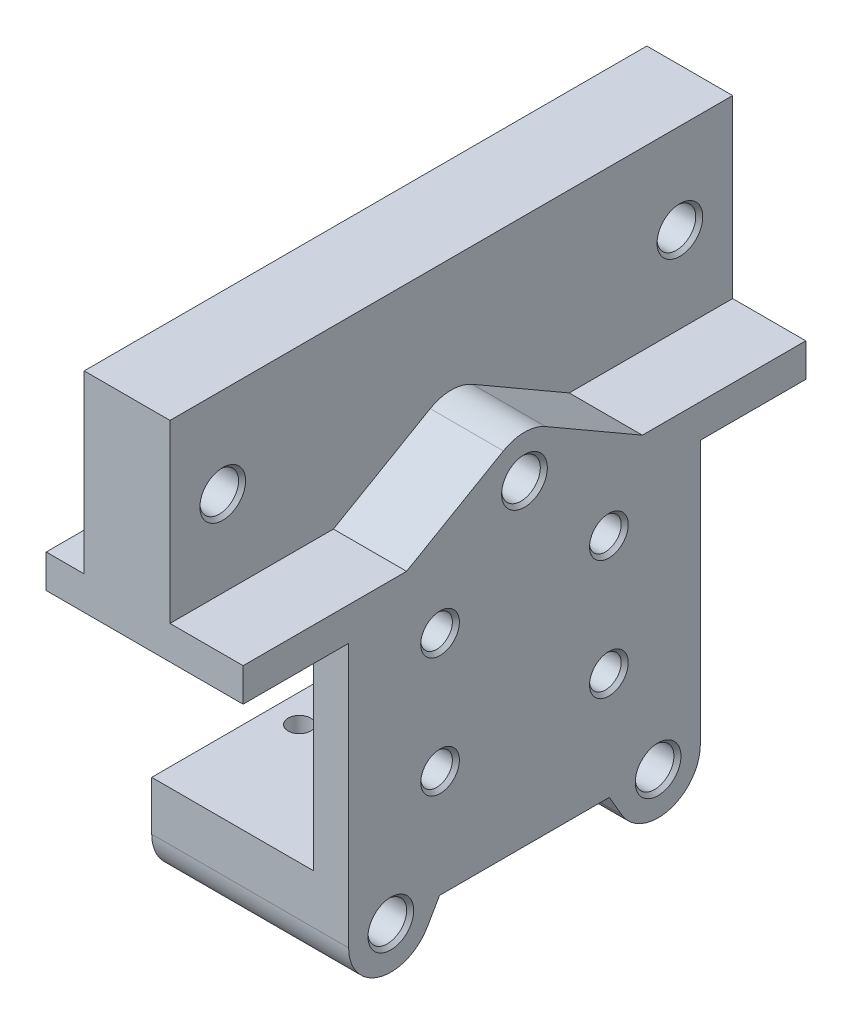
SolidWorks part; units mm, degrees
material "PET"
ref_plane "Front Plane" through (0, 0, 0) normal (0, 0, 1) x (1, 0, 0)
ref_plane "Top Plane" through (0, 0, 0) normal (0, 1, 0) x (1, 0, 0)
ref_plane "Right Plane" through (0, 0, 0) normal (1, 0, 0) x (0, 0, -1)
sketch "Sketch1" plane through (0, 0, 0) normal (0, 0, 1) x (1, 0, 0)
  line L0 (-11.5, 0) -> (16.5, 0)
  line L1 (16.5, 0) -> (16.5, 42.25)
  line L2 (16.5, 42.25) -> (-11.5, 42.25)
  line L3 (11.5, 37.5) -> (11.5, 7)
  line L4 (11.5, 7) -> (-11.5, 7)
  line L8 (-11.5, 7) -> (-11.5, 0)
  line L9 (11.5, 37.5) -> (-11.5, 37.5)
  line L10 (-11.5, 37.5) -> (-11.5, 42.25)
  line L11 (0, 0) -> (0, 42.7189) construction
  point P11 (0, 7)
  dimension "D2" = 23
  dimension "D3" = 5
  dimension "D4" = 7
  dimension "D5" = 30.5
  dimension "D6" = 35.25
extrude "Boss-Extrude1" add sketch "Sketch1" along normal blind 50
sketch "Sketch2" plane through (0, 0, 0) normal (0, -1, 0) x (1, 0, 0)
  line L0 (-11.5, 50) -> (-11.5, 0) construction
  line L3 (-7.5, 17) -> (7.5, 17) construction
  line L4 (-7.5, 17) -> (-7.5, 33) construction
  line L5 (-7.5, 33) -> (7.5, 33) construction
  line L6 (7.5, 17) -> (7.5, 33) construction
  line L7 (-7.5, 17) -> (7.5, 33) construction
  line L8 (-7.5, 33) -> (7.5, 17) construction
  point P5 (0, 25)
  dimension "D1" = 15
  dimension "D2" = 16
  dimension "D3" = 11.5
  dimension "D4" = 25
hole_wizard "Ø3.2 (3.2) Diameter Hole1" positions "Sketch3" profile "Sketch4" hole size "Ø3.2" standard "ANSI Metric" end condition up to next
sketch "Sketch3" plane through (0, 0, 0) normal (0, -1, 0) x (-1, 0, 0)
  point P0 (-7.5, -17)
  point P3 (7.5, -17)
  point P6 (7.5, -33)
  point P9 (-7.5, -33)
sketch "Sketch4" plane through (7.5, 0, 17) normal (1, 0, 0) x (0, 0, -1)
  line L0 (0, 0) -> (0, 7)
  line L1 (0, 7) -> (1.6, 7)
  line L2 (1.6, 7) -> (1.6, 0)
  line L5 (1.6, 0) -> (0, 0)
  line L11 (0, -6.35) -> (0, 107.95) construction
  dimension "Thru Hole Dia." = 3.2
  dimension "Thru Hole Depth" = 7
sketch "Sketch5" plane through (16.5, 0, 0) normal (1, 0, 0) x (0, 0, -1)
  line L0 (-50, 32.25) -> (0, 32.25) construction
  line L1 (-50, 0) -> (-50, 42.25) construction
  line L2 (0, 0) -> (0, 42.25) construction
  line L3 (-50, 42.25) -> (0, 42.25) construction
  line L4 (-50, 15.25) -> (0, 15.25) construction
  line L5 (-13, 32.25) -> (-13, 15.25) construction
  line L6 (-37, 32.25) -> (-37, 15.25) construction
  circle A0 centre (-37, 32.25) radius 2.25
  circle A1 centre (-13, 32.25) radius 2.25
  circle A2 centre (-37, 15.25) radius 2.25
  circle A3 centre (-13, 15.25) radius 2.25
  point P12 (-25, 32.25)
  dimension "D2" = 12
  dimension "D3" = 12
  dimension "D4" = 4.5
  dimension "D5" = 4.5
  dimension "D7" = 4.5
  dimension "D8" = 4.5
  dimension "D1" = 10
  dimension "D6" = 17
extrude "Cut-Extrude1" cut sketch "Sketch5" against normal through all
sketch "Sketch6" plane through (16.5, 0, 0) normal (1, 0, 0) x (0, 0, -1)
  line L1 (-50, 42.25) -> (-65, 42.25)
  line L2 (-50, 42.25) -> (-50, 37.5)
  line L3 (-50, 37.5) -> (-65, 37.5)
  line L4 (-65, 42.25) -> (-65, 37.5)
  line L5 (0, 42.25) -> (15, 42.25)
  line L6 (0, 42.25) -> (0, 37.5)
  line L7 (0, 37.5) -> (15, 37.5)
  line L8 (15, 42.25) -> (15, 37.5)
  dimension "D1" = 4.75
  dimension "D2" = 15
  dimension "D3" = 15
extrude "Boss-Extrude2" add sketch "Sketch6" against normal up to surface (28 mm away) up to face at (-11.5, 39.875, 25)
ref_plane "Plane1" through (0, 0, 25) normal (0, 0, -1) x (-1, 0, 0)
sketch "Sketch8" plane through (0, 42.25, 0) normal (0, 1, 0) x (1, 0, 0)
  line L0 (-11.5, 15) -> (16.5, 15) construction
  line L1 (-6.1, 15) -> (6.1, 15)
  line L2 (-6.1, 15) -> (-6.1, -65)
  line L4 (6.1, 15) -> (6.1, -65)
  line L5 (-11.5, -65) -> (16.5, -65) construction
  line L6 (-6.1, -65) -> (6.1, -65)
  line L10 (-11.5, -65) -> (-11.5, 15) construction
  dimension "D1" = 12.2
  dimension "D3" = 5.4
extrude "Boss-Extrude3" add sketch "Sketch8" along normal blind 25
sketch "Sketch9" plane through (-6.1, 0, 0) normal (-1, 0, 0) x (0, 0, 1)
  line L0 (-7.5, 67.25) -> (-7.5, 42.25) construction
  line L2 (-15, 42.25) -> (65, 42.25) construction
  line L3 (57.5, 67.25) -> (57.5, 42.25) construction
  line L6 (-7.5, 54.45) -> (57.5, 54.45) construction
  line L7 (65, 42.25) -> (-15, 42.25) construction
  line L9 (-15, 67.25) -> (-15, 42.25) construction
  line L10 (-15, 42.25) -> (65, 42.25) construction
  line L11 (-15, 67.25) -> (65, 67.25) construction
  line L12 (65, 67.25) -> (65, 42.25) construction
  circle A0 centre (-7.5, 54.45) radius 2.75
  circle A1 centre (57.5, 54.45) radius 2.75
  dimension "D2" = 5.5
  dimension "D3" = 5.5
  dimension "D1" = 12.2
  dimension "D4" = 7.5
  dimension "D5" = 7.5
extrude "Cut-Extrude2" cut sketch "Sketch9" against normal through all
sketch "Sketch10" plane through (-11.5, 0, 0) normal (-1, 0, 0) x (0, 0, 1)
  line L0 (50, 0) -> (0, 0) construction
  line L1 (0, 7) -> (0, 0) construction
  line L2 (11.1962, -3) -> (12.9282, 0)
  line L3 (25, 0) -> (25, 45) construction
  line L4 (22, 50.1962) -> (8.2369, 42.25)
  line L5 (65, 42.25) -> (-15, 42.25) construction
  line L6 (28, 50.1962) -> (41.7631, 42.25)
  line L7 (38.8038, -3) -> (37.0718, 0)
  line L8 (0, 0) -> (12.9282, 0)
  line L9 (37.0718, 0) -> (50, 0)
  line L10 (8.2369, 42.25) -> (41.7631, 42.25)
  arc A0 (0, 0) -> (11.1962, -3) centre (6, 0) ccw
  arc A1 (38.8038, -3) -> (50, 0) centre (44, 0) ccw
  arc A2 (28, 50.1962) -> (22, 50.1962) centre (25, 45) ccw
  dimension "D1" = 12
  dimension "D2" = 12
  dimension "D3" = 12
  dimension "D4" = 45
  dimension "D5" = 30
  dimension "D6" = 30
  dimension "D7" = 60
  dimension "D8" = 60
extrude "Boss-Extrude4" add sketch "Sketch10" against normal up to surface (28 mm away) up to face at (16.5, 34.5, 13)
sketch "Sketch11" plane through (-11.5, 0, 0) normal (-1, 0, 0) x (0, 0, 1)
  circle A0 centre (25, 45) radius 2.75
  circle A1 centre (44, 0) radius 2.75
  circle A2 centre (6, 0) radius 2.75
  dimension "D1" = 5.5
  dimension "D2" = 5.5
  dimension "D3" = 5.5
extrude "Cut-Extrude3" cut sketch "Sketch11" against normal up to next
chamfer "Chamfer1" distance 0.5 angle 45 18 edges at (6.1, 54.45, -4.75) (6.1, 54.45, 60.25) (16.5, 45, 27.75) (16.5, 17.5, 13) (16.5, 34.5, 13) (16.5, 34.5, 37) (16.5, 17.5, 37) (16.5, 0, 46.75) (16.5, 0, 8.75) (-11.5, -2.75, 6) (-11.5, -2.75, 44) (11.5, 15.25, 34.75) (11.5, 32.25, 34.75) (11.5, 32.25, 10.75) (11.5, 15.25, 10.75) (-11.5, 42.25, 25) (-6.1, 54.45, 60.25) (-6.1, 54.45, -4.75)
